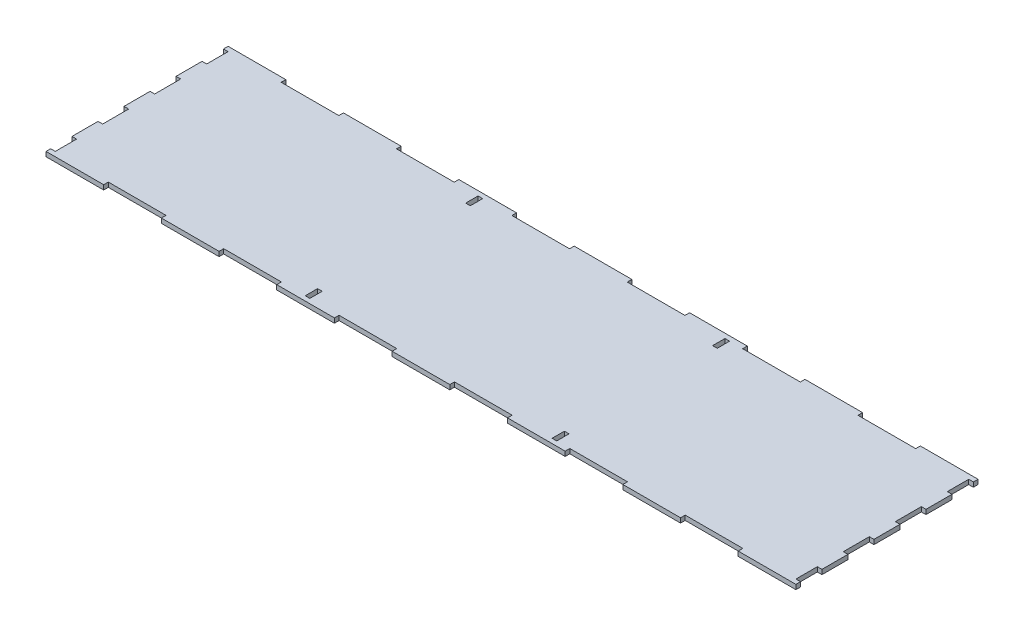
SolidWorks part; units mm, degrees
ref_plane "Front Plane" through (0, 0, 0) normal (0, 0, 1) x (1, 0, 0)
ref_plane "Top Plane" through (0, 0, 0) normal (0, 1, 0) x (1, 0, 0)
ref_plane "Right Plane" through (0, 0, 0) normal (1, 0, 0) x (0, 0, -1)
sketch "Sketch1" plane through (0, 0, 0) normal (0, 1, 0) x (1, 0, 0)
  line L0 (0, 88.9) -> (0, -88.9) construction
  line L1 (-381, 88.9) -> (381, 88.9)
  line L2 (-381, 88.9) -> (-381, -88.9)
  line L3 (-381, -88.9) -> (381, -88.9)
  line L4 (381, 88.9) -> (381, -88.9)
  line L5 (-381, 40.1411) -> (-381, 66.9018)
  line L6 (-381, 66.9018) -> (-385.7625, 66.9018)
  line L7 (-381, 66.9018) -> (-381, 93.6625)
  line L8 (-381, 93.6625) -> (-385.7625, 93.6625)
  line L9 (-385.7625, 66.9018) -> (-385.7625, 93.6625)
  line L14 (-326.4144, -88.9) -> (-385.7625, -88.9)
  line L15 (-326.4144, -88.9) -> (-326.4144, -93.6625)
  line L16 (-326.4144, -93.6625) -> (-385.7625, -93.6625)
  line L17 (-385.7625, -88.9) -> (-385.7625, -93.6625)
  line L18 (381, 66.9018) -> (385.7625, 66.9018)
  line L19 (381, 66.9018) -> (381, 93.6625)
  line L20 (381, 93.6625) -> (385.7625, 93.6625)
  line L21 (385.7625, 66.9018) -> (385.7625, 93.6625)
  line L22 (-326.4144, 88.9) -> (-385.7625, 88.9)
  line L23 (-326.4144, 88.9) -> (-326.4144, 93.6625)
  line L24 (-326.4144, 93.6625) -> (-385.7625, 93.6625)
  line L25 (-385.7625, 88.9) -> (-385.7625, 93.6625)
  line L26 (-381, 40.1411) -> (-385.7625, 40.1411)
  line L27 (-385.7625, 40.1411) -> (-385.7625, 66.9018)
  line L28 (-381, 66.9018) -> (-385.7625, 66.9018)
  line L29 (381, 40.1411) -> (381, 66.9018)
  line L30 (381, 40.1411) -> (385.7625, 40.1411)
  line L31 (385.7625, 40.1411) -> (385.7625, 66.9018)
  line L32 (381, 66.9018) -> (385.7625, 66.9018)
  line L33 (-381, 13.3804) -> (-381, 40.1411)
  line L34 (-381, 13.3804) -> (-385.7625, 13.3804)
  line L35 (-385.7625, 13.3804) -> (-385.7625, 40.1411)
  line L36 (-381, 40.1411) -> (-385.7625, 40.1411)
  line L37 (381, 13.3804) -> (381, 40.1411)
  line L38 (381, 13.3804) -> (385.7625, 13.3804)
  line L39 (385.7625, 13.3804) -> (385.7625, 40.1411)
  line L40 (381, 40.1411) -> (385.7625, 40.1411)
  line L41 (-381, -13.3804) -> (-381, 13.3804)
  line L42 (-381, -13.3804) -> (-385.7625, -13.3804)
  line L43 (-385.7625, -13.3804) -> (-385.7625, 13.3804)
  line L44 (-381, 13.3804) -> (-385.7625, 13.3804)
  line L45 (381, -13.3804) -> (381, 13.3804)
  line L46 (381, -13.3804) -> (385.7625, -13.3804)
  line L47 (385.7625, -13.3804) -> (385.7625, 13.3804)
  line L48 (381, 13.3804) -> (385.7625, 13.3804)
  line L49 (-381, -40.1411) -> (-381, -13.3804)
  line L50 (-381, -40.1411) -> (-385.7625, -40.1411)
  line L51 (-385.7625, -40.1411) -> (-385.7625, -13.3804)
  line L52 (-381, -13.3804) -> (-385.7625, -13.3804)
  line L53 (381, -40.1411) -> (381, -13.3804)
  line L54 (381, -40.1411) -> (385.7625, -40.1411)
  line L55 (385.7625, -40.1411) -> (385.7625, -13.3804)
  line L56 (381, -13.3804) -> (385.7625, -13.3804)
  line L57 (-381, -66.9018) -> (-381, -40.1411)
  line L58 (-381, -66.9018) -> (-385.7625, -66.9018)
  line L59 (-385.7625, -66.9018) -> (-385.7625, -40.1411)
  line L60 (-381, -40.1411) -> (-385.7625, -40.1411)
  line L61 (381, -66.9018) -> (381, -40.1411)
  line L62 (381, -66.9018) -> (385.7625, -66.9018)
  line L63 (385.7625, -66.9018) -> (385.7625, -40.1411)
  line L64 (381, -40.1411) -> (385.7625, -40.1411)
  line L65 (-381, -93.6625) -> (-381, -66.9018)
  line L66 (-381, -93.6625) -> (-385.7625, -93.6625)
  line L67 (-385.7625, -93.6625) -> (-385.7625, -66.9018)
  line L68 (-381, -66.9018) -> (-385.7625, -66.9018)
  line L69 (381, -93.6625) -> (381, -66.9018)
  line L70 (381, -93.6625) -> (385.7625, -93.6625)
  line L71 (385.7625, -93.6625) -> (385.7625, -66.9018)
  line L72 (381, -66.9018) -> (385.7625, -66.9018)
  line L73 (-267.0663, -88.9) -> (-267.0663, -93.6625)
  line L74 (-267.0663, -88.9) -> (-326.4144, -88.9)
  line L75 (-326.4144, -88.9) -> (-326.4144, -93.6625)
  line L76 (-267.0663, -93.6625) -> (-326.4144, -93.6625)
  line L77 (-267.0663, 88.9) -> (-267.0663, 93.6625)
  line L78 (-267.0663, 88.9) -> (-326.4144, 88.9)
  line L79 (-326.4144, 88.9) -> (-326.4144, 93.6625)
  line L80 (-267.0663, 93.6625) -> (-326.4144, 93.6625)
  line L81 (-207.7183, -88.9) -> (-207.7183, -93.6625)
  line L82 (-207.7183, -88.9) -> (-267.0663, -88.9)
  line L83 (-267.0663, -88.9) -> (-267.0663, -93.6625)
  line L84 (-207.7183, -93.6625) -> (-267.0663, -93.6625)
  line L85 (-207.7183, 88.9) -> (-207.7183, 93.6625)
  line L86 (-207.7183, 88.9) -> (-267.0663, 88.9)
  line L87 (-267.0663, 88.9) -> (-267.0663, 93.6625)
  line L88 (-207.7183, 93.6625) -> (-267.0663, 93.6625)
  line L89 (-148.3702, -88.9) -> (-148.3702, -93.6625)
  line L90 (-148.3702, -88.9) -> (-207.7183, -88.9)
  line L91 (-207.7183, -88.9) -> (-207.7183, -93.6625)
  line L92 (-148.3702, -93.6625) -> (-207.7183, -93.6625)
  line L93 (-148.3702, 88.9) -> (-148.3702, 93.6625)
  line L94 (-148.3702, 88.9) -> (-207.7183, 88.9)
  line L95 (-207.7183, 88.9) -> (-207.7183, 93.6625)
  line L96 (-148.3702, 93.6625) -> (-207.7183, 93.6625)
  line L97 (-89.0221, -88.9) -> (-89.0221, -93.6625)
  line L98 (-89.0221, -88.9) -> (-148.3702, -88.9)
  line L99 (-148.3702, -88.9) -> (-148.3702, -93.6625)
  line L100 (-89.0221, -93.6625) -> (-148.3702, -93.6625)
  line L101 (-89.0221, 88.9) -> (-89.0221, 93.6625)
  line L102 (-89.0221, 88.9) -> (-148.3702, 88.9)
  line L103 (-148.3702, 88.9) -> (-148.3702, 93.6625)
  line L104 (-89.0221, 93.6625) -> (-148.3702, 93.6625)
  line L105 (-29.674, -88.9) -> (-29.674, -93.6625)
  line L106 (-29.674, -88.9) -> (-89.0221, -88.9)
  line L107 (-89.0221, -88.9) -> (-89.0221, -93.6625)
  line L108 (-29.674, -93.6625) -> (-89.0221, -93.6625)
  line L109 (-29.674, 88.9) -> (-29.674, 93.6625)
  line L110 (-29.674, 88.9) -> (-89.0221, 88.9)
  line L111 (-89.0221, 88.9) -> (-89.0221, 93.6625)
  line L112 (-29.674, 93.6625) -> (-89.0221, 93.6625)
  line L113 (29.674, -88.9) -> (29.674, -93.6625)
  line L114 (29.674, -88.9) -> (-29.674, -88.9)
  line L115 (-29.674, -88.9) -> (-29.674, -93.6625)
  line L116 (29.674, -93.6625) -> (-29.674, -93.6625)
  line L117 (29.674, 88.9) -> (29.674, 93.6625)
  line L118 (29.674, 88.9) -> (-29.674, 88.9)
  line L119 (-29.674, 88.9) -> (-29.674, 93.6625)
  line L120 (29.674, 93.6625) -> (-29.674, 93.6625)
  line L121 (89.0221, -88.9) -> (89.0221, -93.6625)
  line L122 (89.0221, -88.9) -> (29.674, -88.9)
  line L123 (29.674, -88.9) -> (29.674, -93.6625)
  line L124 (89.0221, -93.6625) -> (29.674, -93.6625)
  line L125 (89.0221, 88.9) -> (89.0221, 93.6625)
  line L126 (89.0221, 88.9) -> (29.674, 88.9)
  line L127 (29.674, 88.9) -> (29.674, 93.6625)
  line L128 (89.0221, 93.6625) -> (29.674, 93.6625)
  line L129 (148.3702, -88.9) -> (148.3702, -93.6625)
  line L130 (148.3702, -88.9) -> (89.0221, -88.9)
  line L131 (89.0221, -88.9) -> (89.0221, -93.6625)
  line L132 (148.3702, -93.6625) -> (89.0221, -93.6625)
  line L133 (148.3702, 88.9) -> (148.3702, 93.6625)
  line L134 (148.3702, 88.9) -> (89.0221, 88.9)
  line L135 (89.0221, 88.9) -> (89.0221, 93.6625)
  line L136 (148.3702, 93.6625) -> (89.0221, 93.6625)
  line L137 (207.7183, -88.9) -> (207.7183, -93.6625)
  line L138 (207.7183, -88.9) -> (148.3702, -88.9)
  line L139 (148.3702, -88.9) -> (148.3702, -93.6625)
  line L140 (207.7183, -93.6625) -> (148.3702, -93.6625)
  line L141 (207.7183, 88.9) -> (207.7183, 93.6625)
  line L142 (207.7183, 88.9) -> (148.3702, 88.9)
  line L143 (148.3702, 88.9) -> (148.3702, 93.6625)
  line L144 (207.7183, 93.6625) -> (148.3702, 93.6625)
  line L145 (267.0663, -88.9) -> (267.0663, -93.6625)
  line L146 (267.0663, -88.9) -> (207.7183, -88.9)
  line L147 (207.7183, -88.9) -> (207.7183, -93.6625)
  line L148 (267.0663, -93.6625) -> (207.7183, -93.6625)
  line L149 (267.0663, 88.9) -> (267.0663, 93.6625)
  line L150 (267.0663, 88.9) -> (207.7183, 88.9)
  line L151 (207.7183, 88.9) -> (207.7183, 93.6625)
  line L152 (267.0663, 93.6625) -> (207.7183, 93.6625)
  line L185 (326.4144, -88.9) -> (326.4144, -93.6625)
  line L186 (326.4144, -88.9) -> (267.0663, -88.9)
  line L187 (267.0663, -88.9) -> (267.0663, -93.6625)
  line L188 (326.4144, -93.6625) -> (267.0663, -93.6625)
  line L189 (326.4144, 88.9) -> (326.4144, 93.6625)
  line L190 (326.4144, 88.9) -> (267.0663, 88.9)
  line L191 (267.0663, 88.9) -> (267.0663, 93.6625)
  line L192 (326.4144, 93.6625) -> (267.0663, 93.6625)
  line L193 (385.7625, -88.9) -> (385.7625, -93.6625)
  line L194 (385.7625, -88.9) -> (326.4144, -88.9)
  line L195 (326.4144, -88.9) -> (326.4144, -93.6625)
  line L196 (385.7625, -93.6625) -> (326.4144, -93.6625)
  line L197 (385.7625, 88.9) -> (385.7625, 93.6625)
  line L198 (385.7625, 88.9) -> (326.4144, 88.9)
  line L199 (326.4144, 88.9) -> (326.4144, 93.6625)
  line L200 (385.7625, 93.6625) -> (326.4144, 93.6625)
  point P8 (0, 88.9)
  point P9 (0, 0)
  dimension "D1" = 762
  dimension "D2" = 177.8
  dimension "D3" = 187.325
  dimension "D5" = 771.525
  dimension "D6" = 26.7607
  dimension "D8" = 59.3481
  dimension "D4" = 7
  dimension "D7" = 13
extrude "Boss-Extrude1" add sketch "Sketch1" along normal blind 4.7625 contours L0 L1 L2 L3 | L126 L0 L122 L3 L4 L1 | L65 L16 L15 L3 | L16 L65 L14 L17 | L84 L81 L3 L73 | L59 L58 L2 L50 | L100 L97 L3 L89 | L43 L42 L2 L34 | L27 L26 L2 L6 | L22 L7 L8 L9 | L23 L24 L7 L1 | L85 L88 L77 L1 | L101 L104 L93 L1 | L117 L120 L109 L1 | L133 L136 L125 L1 | L116 L113 L3 L105 | L132 L129 L3 L121 | L148 L145 L3 L137 | L149 L152 L141 L1 | L21 L20 L19 | L30 L31 L18 L4 | L46 L47 L38 L4 | L62 L63 L54 L4 | L71 L69 L70 | L193 L196 L195 L194 | L197 L200 L199 L198 region at (190.5, 0, 0) region at (-190.5, 0, 0) region at (0, 0, -91.2812) region at (0, 0, 91.2812) region at (-118.6962, 0, -91.2812) region at (118.6962, 0, -91.2812) region at (-118.6962, 0, 91.2812) region at (118.6962, 0, 91.2812) region at (-237.3923, 0, -91.2812) region at (237.3923, 0, -91.2812) region at (-237.3923, 0, 91.2812) region at (237.3923, 0, 91.2812) region at (-353.7072, 0, -91.2812) region at (-353.7072, 0, 91.2812) region at (-383.3812, 0, -91.2812) region at (383.3813, 0, -91.2812) region at (-383.3812, 0, 91.2813) region at (383.3813, 0, 91.2812) region at (-383.3812, 0, -53.5214) region at (383.3813, 0, -53.5214) region at (-383.3812, 0, 53.5214) region at (383.3813, 0, 53.5214) region at (-383.3812, 0, 0) region at (383.3813, 0, 0)
sketch "Sketch2" plane through (0, 4.7625, 0) normal (0, 1, 0) x (1, 0, 0)
  line L0 (-124.6188, 0) -> (124.6188, 0) construction
  line L1 (-129.3812, 15.4404) -> (-124.6188, 15.4404) construction
  line L2 (-129.3812, 15.4404) -> (-129.3812, -15.4404) construction
  line L3 (-129.3812, -15.4404) -> (-124.6188, -15.4404) construction
  line L4 (-124.6188, 15.4404) -> (-124.6188, -15.4404) construction
  line L5 (124.6188, 14.3164) -> (129.3812, 14.3164) construction
  line L6 (124.6188, 14.3164) -> (124.6188, -14.3164) construction
  line L7 (124.6188, -14.3164) -> (129.3812, -14.3164) construction
  line L8 (129.3812, 14.3164) -> (129.3812, -14.3164) construction
  line L9 (-130.175, 24.6215) -> (-123.825, 24.6215) construction
  line L10 (-127, 24.6215) -> (-127, 15.4404) construction
  line L12 (-123.825, 76.2) -> (-119.0625, 76.2)
  line L13 (-123.825, 76.2) -> (-123.825, 88.9)
  line L14 (-123.825, 88.9) -> (-119.0625, 88.9)
  line L15 (-119.0625, 76.2) -> (-119.0625, 88.9)
  line L16 (-123.825, 24.6215) -> (-123.825, 76.2) construction
  line L18 (-119.0625, -88.9) -> (-123.825, -88.9)
  line L19 (-119.0625, -88.9) -> (-119.0625, -76.2)
  line L20 (-119.0625, -76.2) -> (-123.825, -76.2)
  line L21 (-123.825, -88.9) -> (-123.825, -76.2)
  line L31 (-207.7183, 88.9) -> (-148.3702, 88.9) construction
  line L32 (-207.7183, -88.9) -> (-148.3702, -88.9) construction
  line L33 (130.175, 76.2) -> (130.175, 88.9)
  line L34 (130.175, 76.2) -> (134.9375, 76.2)
  line L35 (134.9375, 76.2) -> (134.9375, 88.9)
  line L36 (130.175, 88.9) -> (134.9375, 88.9)
  line L37 (134.9375, -88.9) -> (134.9375, -76.2)
  line L38 (134.9375, -88.9) -> (130.175, -88.9)
  line L39 (130.175, -88.9) -> (130.175, -76.2)
  line L40 (134.9375, -76.2) -> (130.175, -76.2)
  line L41 (123.825, 24.6215) -> (130.175, 24.6215) construction
  line L42 (127, 24.6215) -> (127, 14.3164) construction
  line L43 (130.175, 24.6215) -> (130.175, 76.2) construction
  point P10 (0, 0)
  point P43 (127, 14.3164)
  dimension "D1" = 4.7625
  dimension "D2" = 6.35
  dimension "D4" = 4.7625
  dimension "D5" = 12.7
  dimension "D3" = 254
  dimension "D6" = 2
extrude "Cut-Extrude1" cut sketch "Sketch2" against normal through all
equation "\"Height\"= 12in"
equation "\"Depth\"= 7in"
equation "\"WallThickness\"= 0.1875in"
equation "\"FloorThickness\"= 0.1875in"
equation "\"D1@Sketch1\"=\"Width\""
equation "\"D2@Sketch1\"=\"Depth\""
equation "\"D3@Sketch1\"=\"D2@Sketch1\"+2*\"WallThickness\""
equation "\"D5@Sketch1\"=\"D1@Sketch1\"+2*\"WallThickness\""
equation "\"D6@Sketch1\"=\"D3@Sketch1\"/\"D4@Sketch1\""
equation "\"D8@Sketch1\"=\"D5@Sketch1\"/\"D7@Sketch1\""
equation "\"D1@Boss-Extrude1\"=\"FloorThickness\""
equation "\"D1@Sketch2\"=\"WallThickness\""
equation "\"D2@Sketch2\"=\"WallThickness\"+(1/16in)"
equation "\"D4@Sketch2\"=\"WallThickness\""
equation "\"Width\" = 30in"
